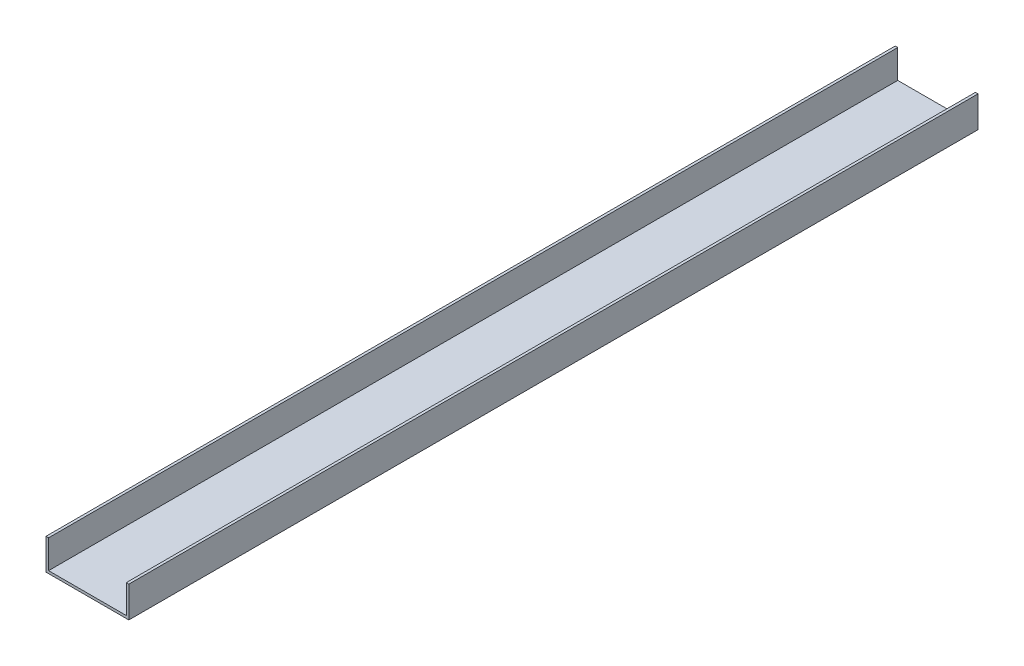
SolidWorks part; units mm, degrees
ref_plane "Front" through (0, 0, 0) normal (0, 0, 1) x (1, 0, 0)
ref_plane "Top" through (0, 0, 0) normal (0, 1, 0) x (1, 0, 0)
ref_plane "Right" through (0, 0, 0) normal (1, 0, 0) x (0, 0, -1)
sketch "Sketch1" plane through (0, 0, 0) normal (0, 0, 1) x (1, 0, 0)
  line L0 (0, -9.525) -> (0, 9.525) construction
  line L1 (-25.4, 0) -> (25.4, 0) construction
  line L2 (23.8125, 9.525) -> (-23.8125, 9.525) construction
  line L3 (-25.4, -9.525) -> (25.4, -9.525)
  line L4 (-25.4, -9.525) -> (-25.4, 9.525)
  line L5 (-25.4, 9.525) -> (25.4, 9.525)
  line L6 (25.4, -9.525) -> (25.4, 9.525)
  line L7 (-25.4, -9.525) -> (25.4, 9.525) construction
  line L8 (-25.4, 9.525) -> (25.4, -9.525) construction
  line L9 (-23.8125, -9.525) -> (23.8125, -9.525)
  point P3 (0, 0)
  point P4 (0, 0)
  point P8 (0, 0)
  point P13 (25.4, -7.9375)
  point P17 (0, 9.525)
  point P20 (0, -9.525)
  dimension "Outside Width" = 50.8
  dimension "Outside Height" = 19.05
  dimension "Inside Height" = 17.4625
  dimension "Wall Thickness" = 1.5875
  dimension "Inside Width" = 47.625
sketch "Sketch2" plane through (0, 0, 0) normal (1, 0, 0) x (0, 0, -1)
  line L0 (-260.35, 0) -> (260.35, 0) construction
  dimension "Length" = 520.7
sketch "Sketch3" plane through (0, 0, 0) normal (0, 0, 1) x (1, 0, 0)
  line L0 (-25.4, 9.525) -> (-25.4, -9.525)
  line L1 (-25.4, -9.525) -> (25.4, -9.525)
  line L2 (25.4, -9.525) -> (25.4, 9.525)
  line L3 (25.4, 9.525) -> (23.8125, 9.525)
  line L4 (23.8125, 9.525) -> (23.8125, -7.9375)
  line L5 (23.8125, -7.9375) -> (-23.8125, -7.9375)
  line L6 (-23.8125, -7.9375) -> (-23.8125, 9.525)
  line L7 (-23.8125, 9.525) -> (-25.4, 9.525)
  line L8 (-23.8125, -7.9375) -> (-23.8125, -9.525) construction
  dimension "D1" = 19.05
  dimension "D2" = 50.8
  dimension "D3" = 1.5875
extrude "Boss-Extrude2" add sketch "Sketch3" along normal mid plane 520.7
sketch "Reference Sketch1" plane through (0, 0, 0) normal (1, 0, 0) x (0, 0, -1)
  line L0 (-260.35, 0) -> (260.35, 0) construction
  point P0 (-227.0125, 0)
  point P1 (227.0125, 0)
  dimension "D1" = 33.3375
  dimension "D2" = 33.3375
equation "\"D1@Sketch3\" = \"Outside Height@Sketch1\""
equation "\"D2@Sketch3\" = \"Outside Width@Sketch1\""
equation "\"D3@Sketch3\" = \"Wall Thickness@Sketch1\""
equation "\"D1@Reference Sketch1\"=\"Outside Height@Sketch1\" * 1.75"
equation "\"D2@Reference Sketch1\" = \"D1@Reference Sketch1\""
equation "\"D1@Boss-Extrude2\" = \"Length@Sketch2\""
equation "\"Inside Height@Sketch1\"=\"Outside Height@Sketch1\"-\"Wall Thickness@Sketch1\""
equation "\"Inside Width@Sketch1\"=\"Outside Width@Sketch1\"-\"Wall Thickness@Sketch1\"*2"
